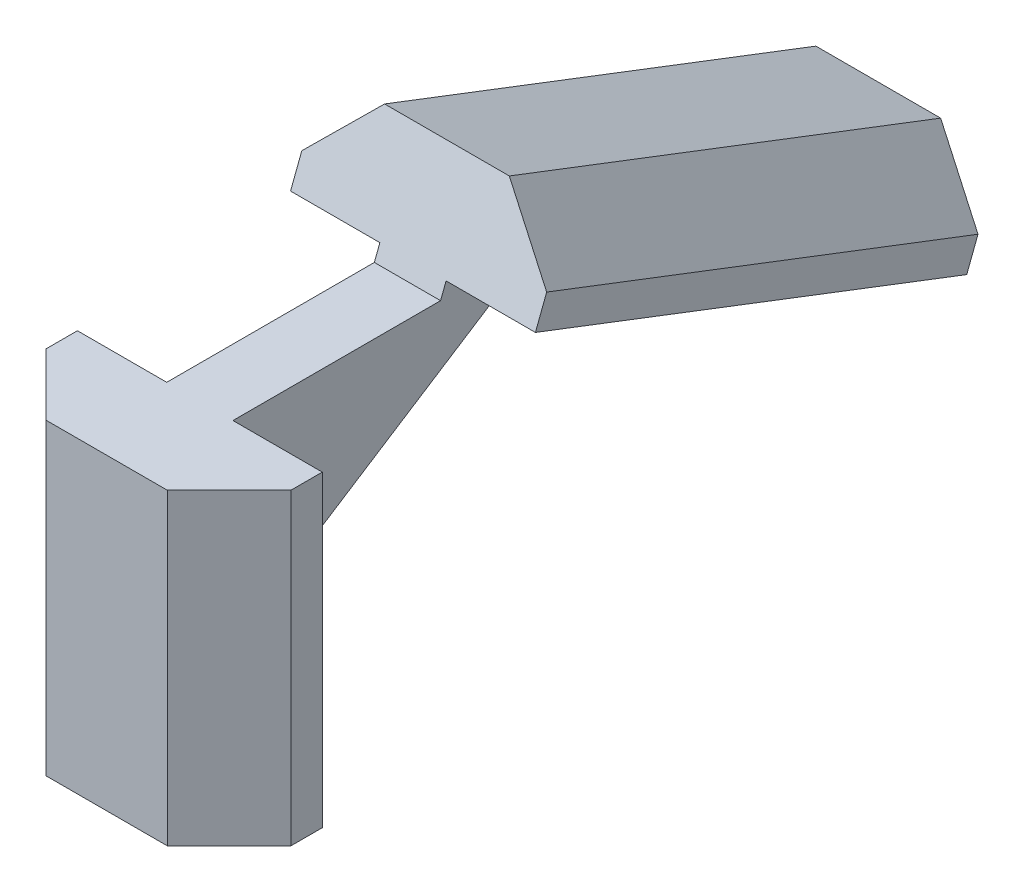
SolidWorks part; units mm, degrees
ref_plane "Front Plane" through (0, 0, 0) normal (0, 0, 1) x (1, 0, 0)
ref_plane "Top Plane" through (0, 0, 0) normal (0, 1, 0) x (1, 0, 0)
ref_plane "Right Plane" through (0, 0, 0) normal (1, 0, 0) x (0, 0, -1)
sketch "Sketch1" plane through (0, 0, 0) normal (0, 1, 0) x (1, 0, 0)
  line L0 (-3.9407, -6.0493) -> (3.9407, -6.0493)
  line L1 (7.95, 0) -> (7.95, -2.04)
  line L2 (7.95, -2.04) -> (3.9407, -6.0493)
  line L4 (0, 0) -> (0, 4.5954) construction
  line L5 (-7.95, -2.04) -> (-3.9407, -6.0493)
  line L6 (-7.95, 0) -> (-7.95, -2.04)
  line L7 (-7.95, 0) -> (7.95, 0)
  dimension "D1" = 15.9
  dimension "D2" = 2.04
  dimension "D3" = 5.67
extrude "Boss-Extrude1" add sketch "Sketch1" against normal blind 20 contours L7 L1 L2 L0 L5 L6
ref_plane "Plane1" through (0, 0, 0) normal (1, 0, 0) x (0, 0, -1)
sketch "Sketch2" plane through (0, 0, 0) normal (1, 0, 0) x (0, 0, -1)
  line L1 (0, -20) -> (0, 0) construction
  line L10 (5.1098, 0) -> (23.7814, -7.1674)
  line L12 (5.1098, 0) -> (6.1849, 2.8007)
  line L13 (6.1849, 2.8007) -> (24.8565, -4.3666)
  line L14 (24.8565, -4.3666) -> (23.7814, -7.1674)
  point P0 (24.8212, -4.9662)
  dimension "D1" = 69
  dimension "D2" = 3
  dimension "D3" = 20
  dimension "D4" = 5.1098
sketch "Sketch4" plane through (0, 0, 0) normal (1, 0, 0) x (0, 0, -1)
  line L0 (0, 0) -> (13.4811, 0)
  line L1 (6.1849, 2.8007) -> (24.8565, -4.3666) construction
  line L2 (13.4811, 0) -> (17.2781, -1.4575)
  line L3 (17.2781, -1.4575) -> (0, -12.5397)
  line L4 (0, -20) -> (0, 0) construction
  line L5 (0, -12.5397) -> (0, 0)
  point P6 (15.1028, -7.1243)
extrude "Boss-Extrude3" add sketch "Sketch4" along normal mid plane 4.3 contours L5 L0 L2 L3
ref_plane "Plane2" through (0, 5.4439, -2.0897) normal (0, 0.9336, -0.3584) x (1, 0, 0)
sketch "Sketch6" plane through (0, 5.4439, -2.0897) normal (0, 0.9336, -0.3584) x (1, 0, 0)
  line L0 (-2.15, 16.6528) -> (2.15, 16.6528)
  line L1 (2.15, 16.6528) -> (2.15, 12.5857)
  line L2 (2.15, 12.5857) -> (-2.15, 12.5857)
  line L3 (-2.15, 12.5857) -> (-2.15, 16.6528)
extrude "Boss-Extrude4" add sketch "Sketch6" against normal up to surface (1 mm away) contours L3 L0 L1 L2 up to face at (0, -0.7288, -15.3796)
ref_plane "Plane3" through (0, -4.5103, -11.7497) normal (0, 0.3584, 0.9336) x (1, 0, 0)
sketch "Sketch8" plane through (0, -4.5103, -11.7497) normal (0, 0.3584, 0.9336) x (1, 0, 0)
  line L0 (-4.05, 11.9869) -> (4.05, 11.9869)
  line L1 (55, 5.8312) -> (-55, 5.8312) construction
  line L2 (7.95, 5.8312) -> (7.95, 7.8712)
  line L3 (7.95, 7.8712) -> (4.05, 11.9869)
  line L4 (-7.95, 5.8312) -> (-7.95, 7.8712)
  line L5 (0, 5.8312) -> (0, 14.4021) construction
  line L6 (-7.95, 7.8712) -> (-4.05, 11.9869)
  line L7 (7.95, 5.8312) -> (-7.95, 5.8312)
  dimension "D1" = 15.9
  dimension "D2" = 5.67
  dimension "D3" = 2.04
  dimension "D4" = 8.1
extrude "Boss-Extrude5" add sketch "Sketch8" against normal blind 30 contours L7 L4 L6 L0 L3 L2
